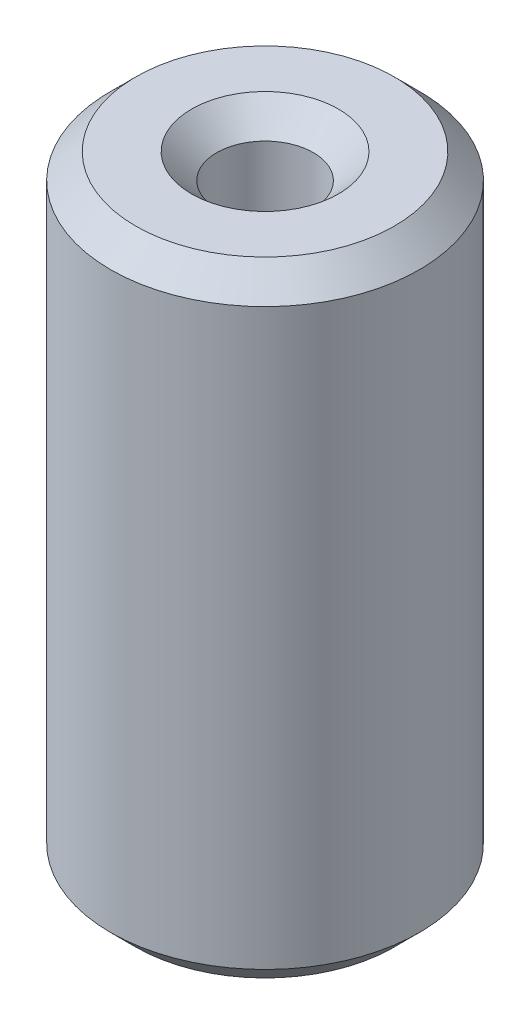
SolidWorks part; units mm, degrees
ref_plane "Front Plane" through (0, 0, 0) normal (0, 0, 1) x (1, 0, 0)
ref_plane "Top Plane" through (0, 0, 0) normal (0, 1, 0) x (1, 0, 0)
ref_plane "Right Plane" through (0, 0, 0) normal (1, 0, 0) x (0, 0, -1)
sketch "Sketch1" plane through (0, 0, 0) normal (0, 1, 0) x (1, 0, 0)
  circle A0 centre (0, 0) radius 5
  dimension "SLEEVE_OD" = 10
extrude "Boss-Extrude1" add sketch "Sketch1" along normal blind 20.2131
sketch "Sketch2" plane through (0, 0, 0) normal (0, 1, 0) x (1, 0, 0)
  circle A0 centre (0, 0) radius 1.5658
  dimension "BORE_D" = 3.1316
extrude "Cut-Extrude1" cut sketch "Sketch2" along normal through all
chamfer "Chamfer1" distance 0.8143 angle 45 4 edges at (0, 20.2131, 1.5658) (0, 0, 1.5658) (0, 0, 5) (0, 20.2131, 5)
